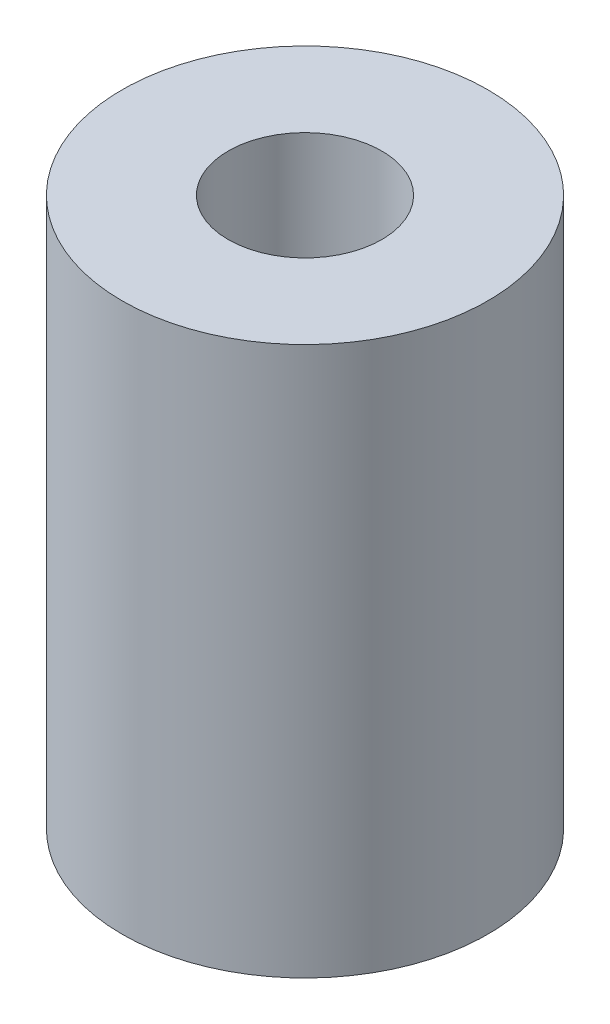
SolidWorks part; units mm, degrees
material "5052-H34"
ref_plane "正面" through (0, 0, 0) normal (0, 0, 1) x (1, 0, 0)
ref_plane "平面" through (0, 0, 0) normal (0, 1, 0) x (1, 0, 0)
ref_plane "右側面" through (0, 0, 0) normal (1, 0, 0) x (0, 0, -1)
sketch "ｽｹｯﾁ1" plane through (0, 0, 0) normal (0, 1, 0) x (1, 0, 0)
  circle A0 centre (0, 0) radius 2.1
  circle A1 centre (0, 0) radius 5
  dimension "D1" = 4.2
  dimension "D2" = 10
extrude "ﾎﾞｽ - 押し出し1" add sketch "ｽｹｯﾁ1" along normal blind 15
